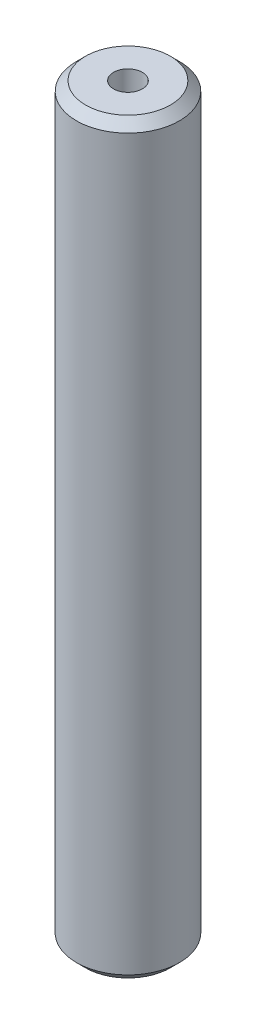
SolidWorks part; units mm, degrees
ref_plane "Front Plane" through (0, 0, 0) normal (0, 0, 1) x (1, 0, 0)
ref_plane "Top Plane" through (0, 0, 0) normal (0, 1, 0) x (1, 0, 0)
ref_plane "Right Plane" through (0, 0, 0) normal (1, 0, 0) x (0, 0, -1)
sketch "Sketch1" plane through (0, 0, 0) normal (0, 1, 0) x (1, 0, 0)
  circle A0 centre (0, 0) radius 10
  dimension "SHAFT_OD" = 20
extrude "Boss-Extrude1" add sketch "Sketch1" along normal blind 145.1236
sketch "Sketch2" plane through (0, 0, 0) normal (0, 1, 0) x (1, 0, 0)
  circle A0 centre (0, 0) radius 2.7962
  dimension "BORE_D" = 5.5925
extrude "Cut-Extrude1" cut sketch "Sketch2" along normal through all
chamfer "Chamfer1" distance 1.7699 angle 45 2 edges at (0, 145.1236, 10) (0, 0, 10)
